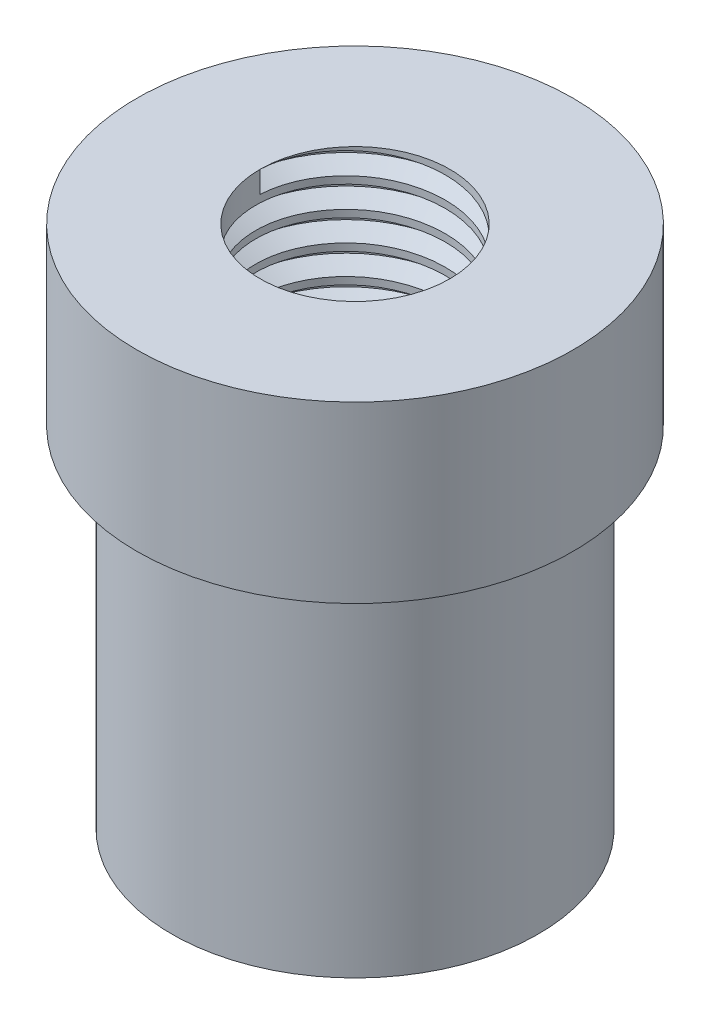
SolidWorks part; units mm, degrees
material "AISI 4130 Steel, annealed at 865C"
ref_plane "Front Plane" through (0, 0, 0) normal (0, 0, 1) x (1, 0, 0)
ref_plane "Top Plane" through (0, 0, 0) normal (0, 1, 0) x (1, 0, 0)
ref_plane "Right Plane" through (0, 0, 0) normal (1, 0, 0) x (0, 0, -1)
sketch "Sketch1" plane through (0, 0, 0) normal (0, 1, 0) x (1, 0, 0)
  circle A0 centre (0, 0) radius 7.9375
  dimension "D1" = 15.875
extrude "Boss-Extrude1" add sketch "Sketch1" along normal blind 6.35
sketch "Sketch2" plane through (0, 0, 0) normal (0, -1, 0) x (1, 0, 0)
  circle A0 centre (0, 0) radius 6.6675
  dimension "D1" = 13.335
extrude "Boss-Extrude2" add sketch "Sketch2" along normal blind 12.7
sketch "Sketch5" plane through (0, 6.35, 0) normal (0, 1, 0) x (1, 0, 0)
  circle A0 centre (0, 0) radius 3.4544
  dimension "D1" = 6.9088
extrude "Cut-Extrude1" cut sketch "Sketch5" against normal through all both and the other way through all
thread "Thread1" pitch 1.0583 method cut profile "Thread Profile2" start angle 0, offset 0, length 50.8, pitch 1.0583, diameter 6.9088
ref_plane "Plane2" through (-3.4544, 6.35, 0) normal (0, 0, 1) x (-1, 0, 0)
sketch "Thread Profile2" plane through (-3.4544, 6.35, 0) normal (0, 0, 1) x (-1, 0, 0)
  line L0 (0, 0) -> (0, 1.0583) construction
  line L1 (0, 0) -> (0.5728, 0.3307)
  line L2 (0.5728, 0.3307) -> (0.5728, 0.463)
  line L3 (0.5728, 0.463) -> (0, 0.7937)
  line L4 (0.5728, 0.3969) -> (0, 0.3969) construction
  line L11 (0, 0) -> (0, 0.7937)
  point P2 (0, 0)
  dimension "Pitch" = 1.0583
  dimension "Profile_Angle" = 60
  dimension "Profile_Land" = 0.1323
  dimension "Profile_Height" = 0.5728
